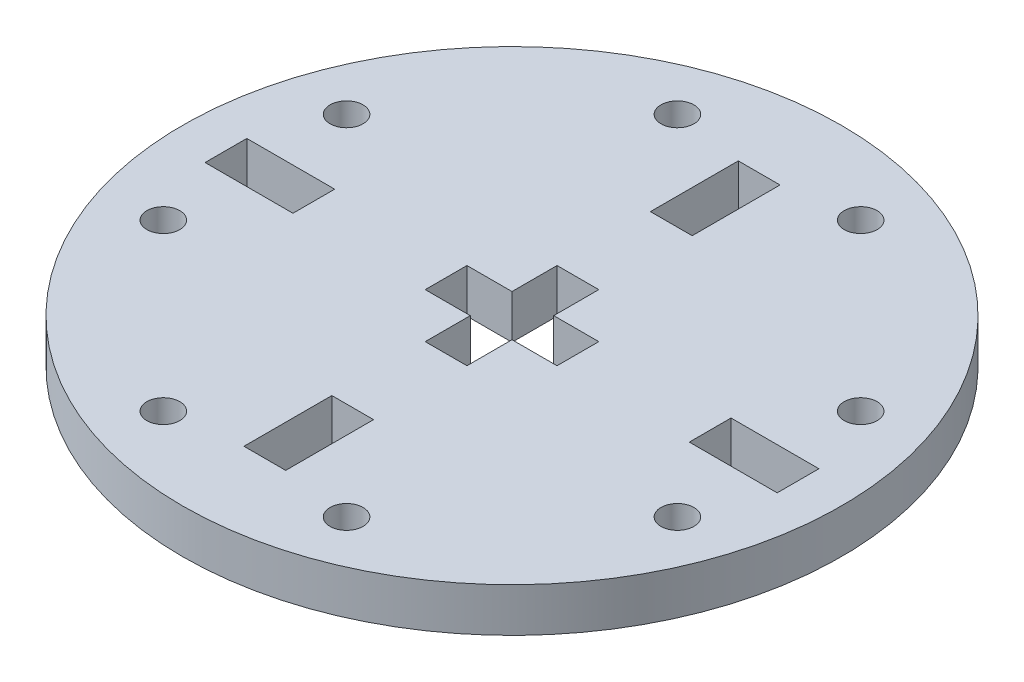
SolidWorks part; units mm, degrees
ref_plane "Front Plane" through (0, 0, 0) normal (0, 0, 1) x (1, 0, 0)
ref_plane "Top Plane" through (0, 0, 0) normal (0, 1, 0) x (1, 0, 0)
ref_plane "Right Plane" through (0, 0, 0) normal (1, 0, 0) x (0, 0, -1)
sketch "Sketch1" plane through (0, 0, 0) normal (0, 1, 0) x (1, 0, 0)
  line L1 (-1.9, 0) -> (1.9, 0)
  line L2 (-1.9, 0) -> (-1.9, 6)
  line L3 (-1.9, 6) -> (1.9, 6)
  line L4 (1.9, 0) -> (1.9, 6)
  line L5 (-1.9, 22.5) -> (1.9, 22.5)
  line L6 (-1.9, 22.5) -> (-1.9, 14.5)
  line L7 (-1.9, 14.5) -> (1.9, 14.5)
  line L8 (1.9, 22.5) -> (1.9, 14.5)
  line L9 (0, 1.9) -> (6, 1.9)
  line L10 (0, 1.9) -> (0, -1.9)
  line L11 (0, -1.9) -> (6, -1.9)
  line L12 (6, 1.9) -> (6, -1.9)
  line L13 (18.04, 1.9) -> (26.04, 1.9)
  line L14 (18.04, 1.9) -> (18.04, -1.9)
  line L15 (18.04, -1.9) -> (26.04, -1.9)
  line L16 (26.04, 1.9) -> (26.04, -1.9)
  circle A0 centre (0, 0) radius 30
  circle A1 centre (8.34, 23.4) radius 1.5
  point P11 (0, 14.5)
  point P12 (0, 6)
  point P17 (0, 0)
  dimension "D1" = 60
  dimension "D10" = 3
  dimension "D12" = 0.9
  dimension "D2" = 3.8
  dimension "D3" = 6
  dimension "D4" = 8.5
  dimension "D5" = 8
  dimension "D6" = 6
  dimension "D7" = 3.8
  dimension "D8" = 12.04
  dimension "D9" = 8
  dimension "D11" = 6.44
extrude "Boss-Extrude1" add sketch "Sketch1" along normal blind 4 contours A0
extrude "Cut-Extrude3" cut sketch "Sketch1<4>" against normal through all from surface contours L8 L7 L6 L5 | L4 L3 L2 L1 | L12 L11 L10 L9 | L14 L15 L16 L13 starting at face at (0, 4, 30)
sketch "Sketch1<4>" plane through (0, 0, 0) normal (0, 1, 0) x (1, 0, 0) same geometry as "Sketch1"
extrude "Cut-Extrude5" cut sketch "Sketch1<5>" against normal through all from surface contours A1 starting at face at (1.5, 4, -1.5)
sketch "Sketch1<5>" plane through (0, 0, 0) normal (0, 1, 0) x (1, 0, 0) same geometry as "Sketch1"
mirror "Mirror1" about plane through (0, 0, 0) normal (1, 0, 0) of "Cut-Extrude5"
pattern_circular "CirPattern2" count 4 over 360 about axis through (0, 0, 0) along (0, -1, 0) of "Cut-Extrude5", "Mirror1"
pattern_circular "CirPattern3" count 2 over 360 about axis through (0, 0, 0) along (0, -1, 0) of "Cut-Extrude3" reverse direction yes
